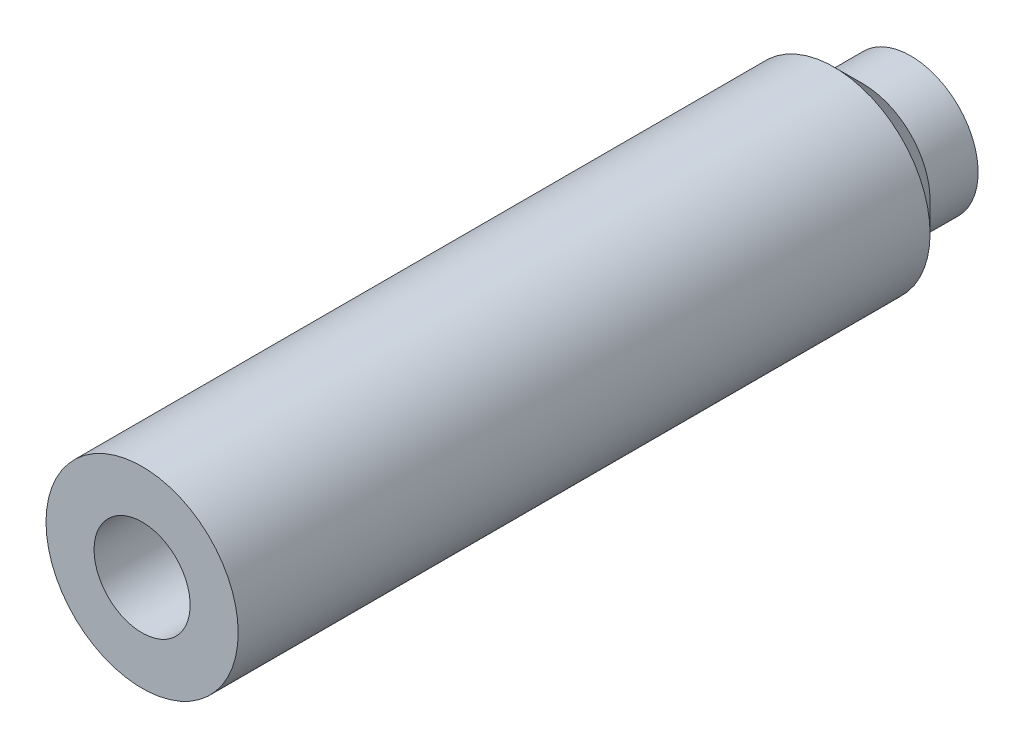
SolidWorks part; units mm, degrees
material "6061-T6 (SS)"
ref_plane "Front" through (0, 0, 0) normal (0, 0, 1) x (1, 0, 0)
ref_plane "Top" through (0, 0, 0) normal (0, 1, 0) x (1, 0, 0)
ref_plane "Right" through (0, 0, 0) normal (1, 0, 0) x (0, 0, -1)
sketch "Sketch1" plane through (0, 0, 0) normal (0, 0, 1) x (1, 0, 0)
  circle A0 centre (0, 0) radius 6.35
  dimension "D1" = 12.7
extrude "Boss-Extrude1" add sketch "Sketch1" along normal blind 50.8
sketch "Sketch2" plane through (0, 0, 0) normal (0, 0, -1) x (-1, 0, 0)
  circle A0 centre (0, 0) radius 4.445
  circle A1 centre (0, 0) radius 6.35 construction
  circle A2 centre (0, 0) radius 6.35
  dimension "D1" = 8.89
extrude "Cut-Extrude1" cut sketch "Sketch2" against normal blind 3.175
chamfer "Chamfer1" distance 1.905 angle 45 1 edges at (-6.35, 0, 3.175)
sketch "Sketch3" plane through (0, 0, 0) normal (0, 0, -1) x (-1, 0, 0)
  circle A0 centre (0, 0) radius 3.175
  dimension "D1" = 6.35
extrude "Cut-Extrude2" cut sketch "Sketch3" against normal through all
